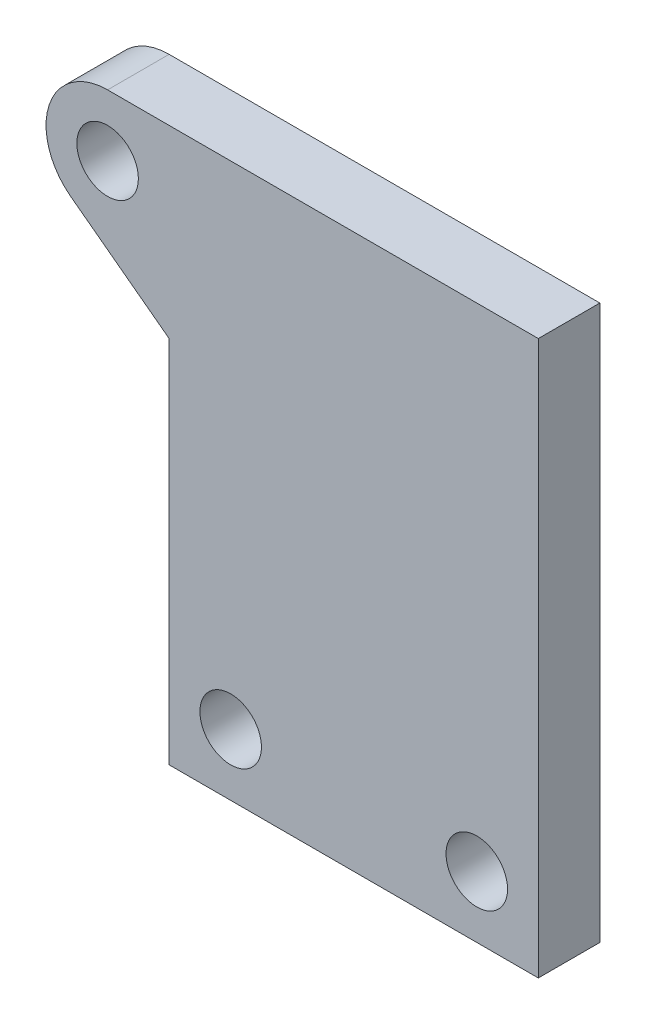
SolidWorks part; units mm, degrees
ref_plane "Front Plane" through (0, 0, 0) normal (0, 0, 1) x (1, 0, 0)
ref_plane "Top Plane" through (0, 0, 0) normal (0, 1, 0) x (1, 0, 0)
ref_plane "Right Plane" through (0, 0, 0) normal (1, 0, 0) x (0, 0, -1)
sketch "Sketch1" plane through (0, 0, 0) normal (0, 0, 1) x (1, 0, 0)
  line L0 (-10, 0) -> (10, 0) construction
  line L1 (-15, -5) -> (15, -5)
  line L2 (-15, -5) -> (-15, 25)
  line L4 (15, -5) -> (15, 40)
  line L5 (-15, 25) -> (-25, 25) construction
  line L10 (-25, 25) -> (-25, 35) construction
  line L11 (-20, 40) -> (15, 40)
  line L14 (-15, 25) -> (-23, 31)
  circle A0 centre (-10, 0) radius 2.5
  circle A1 centre (10, 0) radius 2.5
  circle A2 centre (-20, 35) radius 2.5
  arc A3 (-25, 35) -> (-20, 40) centre (-20, 35) cw
  arc A4 (-25, 35) -> (-23, 31) centre (-20, 35) ccw
  point P9 (0, -5)
  point P11 (15, 40)
  point P18 (-25, 40)
  point P21 (-23.0236, 31.0388)
  point P22 (-23.2558, 31.4305)
  point P23 (0, 0)
  point P24 (15, 39.8141)
  dimension "D2" = 5
  dimension "D8" = 5
  dimension "D11" = 5
  dimension "D1" = 20
  dimension "D3" = 5
  dimension "D4" = 30
  dimension "D5" = 30
  dimension "D6" = 15
  dimension "D7" = 10
  dimension "D9" = 5
  dimension "D10" = 5
extrude "Boss-Extrude1" add sketch "Sketch1" along normal blind 5
